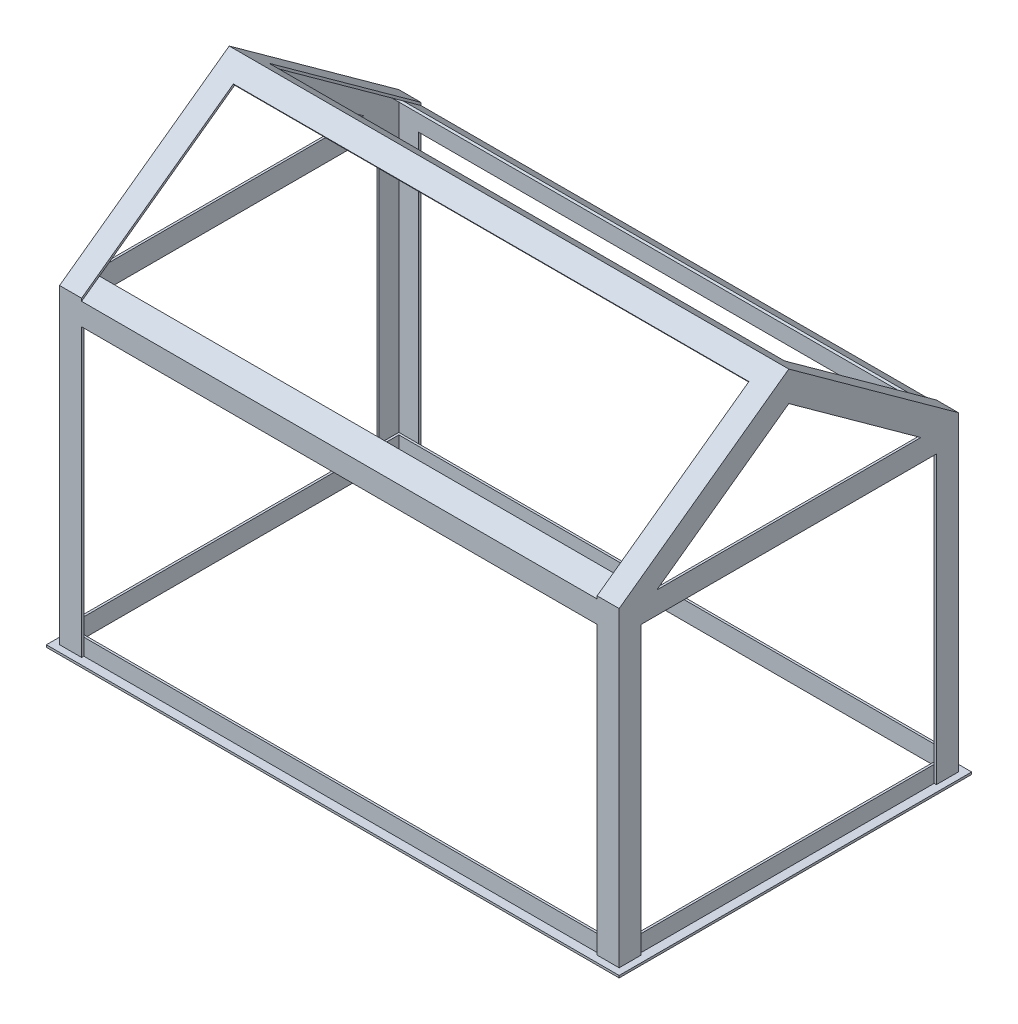
SolidWorks part; units mm, degrees
material "1350 Legierung"
ref_plane "Ebene vorne" through (0, 0, 0) normal (0, 0, 1) x (1, 0, 0)
ref_plane "Ebene oben" through (0, 0, 0) normal (0, 1, 0) x (1, 0, 0)
ref_plane "Ebene rechts" through (0, 0, 0) normal (1, 0, 0) x (0, 0, -1)
sketch "Skizze1" plane through (0, 0, 0) normal (0, 1, 0) x (1, 0, 0)
  line L1 (0, 0) -> (520, 0)
  line L2 (0, 0) -> (0, 320)
  line L3 (0, 320) -> (520, 320)
  line L4 (520, 0) -> (520, 320)
  line L5 (10, 310) -> (510, 310)
  line L6 (10, 310) -> (10, 10)
  line L7 (10, 10) -> (510, 10)
  line L8 (510, 310) -> (510, 10)
  dimension "D1" = 10
  dimension "D2" = 10
  dimension "D3" = 520
  dimension "D4" = 320
  dimension "D5" = 10
  dimension "D6" = 10
extrude "Aufsatz-Linear austragen1" add sketch "Skizze1" along normal blind 2
sketch "Skizze2" plane through (0, 2, 0) normal (0, 1, 0) x (1, 0, 0)
  line L1 (10, 310) -> (510, 310)
  line L2 (10, 310) -> (10, 10)
  line L3 (10, 10) -> (510, 10)
  line L4 (510, 310) -> (510, 10)
  line L5 (8, 312) -> (512, 312)
  line L6 (8, 312) -> (8, 8)
  line L7 (8, 8) -> (512, 8)
  line L8 (512, 312) -> (512, 8)
  dimension "D1" = 2
  dimension "D2" = 2
  dimension "D3" = 2
  dimension "D4" = 2
extrude "Aufsatz-Linear austragen2" add sketch "Skizze2" along normal blind 15
sketch "Skizze3" plane through (0, 2, 0) normal (0, 1, 0) x (1, 0, 0)
  line L0 (8, 294) -> (6, 294)
  line L1 (8, 312) -> (8, 8) construction
  line L2 (6, 294) -> (6, 314)
  line L3 (6, 314) -> (26, 314)
  line L4 (26, 314) -> (26, 312)
  line L5 (512, 312) -> (8, 312) construction
  line L6 (26, 312) -> (8, 312)
  line L7 (8, 312) -> (8, 294)
  line L8 (260, 341.2659) -> (260, -42.352) construction
  line L9 (-21.5346, 160) -> (593.4367, 160) construction
  line L10 (512, 312) -> (512, 294)
  line L11 (494, 312) -> (512, 312)
  line L12 (494, 314) -> (494, 312)
  line L13 (514, 314) -> (494, 314)
  line L14 (514, 294) -> (514, 314)
  line L15 (512, 294) -> (514, 294)
  line L16 (512, 26) -> (514, 26)
  line L17 (514, 26) -> (514, 6)
  line L18 (514, 6) -> (494, 6)
  line L19 (494, 6) -> (494, 8)
  line L20 (494, 8) -> (512, 8)
  line L21 (512, 8) -> (512, 26)
  line L22 (8, 8) -> (8, 26)
  line L23 (26, 8) -> (8, 8)
  line L24 (26, 6) -> (26, 8)
  line L25 (6, 6) -> (26, 6)
  line L26 (6, 26) -> (6, 6)
  line L27 (8, 26) -> (6, 26)
  line L28 (8, 8) -> (512, 8) construction
  line L29 (512, 8) -> (512, 312) construction
  line L30 (512, 8) -> (512, 312) construction
  dimension "D1" = 2
  dimension "D2" = 20
extrude "Aufsatz-Linear austragen3" add sketch "Skizze3" along normal blind 280
sketch "Skizze4" plane through (26, 0, 0) normal (1, 0, 0) x (0, 0, -1)
  line L0 (8, 282) -> (8, 17) construction
  line L1 (6, 282) -> (8, 282)
  line L2 (6, 282) -> (6, 262)
  line L3 (6, 262) -> (8, 262)
  line L4 (8, 282) -> (8, 262)
  dimension "D1" = 20
extrude "Aufsatz-Linear austragen4" add sketch "Skizze4" along normal up to next
ref_plane "Ebene1" through (0, 0, -160) normal (0, 0, 1) x (1, 0, 0)
mirror "Spiegeln1" about plane through (0, 0, -160) normal (0, 0, 1) of "Aufsatz-Linear austragen4"
sketch "Skizze5" plane through (0, 0, -294) normal (0, 0, 1) x (1, 0, 0)
  line L0 (514, 282) -> (514, 2) construction
  line L1 (512, 282) -> (514, 282)
  line L2 (512, 282) -> (512, 262)
  line L3 (512, 262) -> (514, 262)
  line L4 (514, 282) -> (514, 262)
  dimension "D1" = 20
extrude "Aufsatz-Linear austragen5" add sketch "Skizze5" along normal up to next
ref_plane "Ebene2" through (260, 0, 0) normal (1, 0, 0) x (0, 0, -1)
mirror "Spiegeln2" about plane through (260, 0, 0) normal (1, 0, 0) of "Aufsatz-Linear austragen5"
sketch "Skizze7" plane through (6, 0, 0) normal (-1, 0, 0) x (0, 0, 1)
  line L0 (-314, 282) -> (-160, 393.2834)
  line L1 (-160, 393.2834) -> (-6, 282)
  line L2 (-6, 282) -> (-40.147, 282)
  line L3 (-314, 282) -> (-6, 282) construction
  line L4 (-40.147, 282) -> (-160, 368.6081)
  line L5 (-160, 368.6081) -> (-279.853, 282)
  line L6 (-279.853, 282) -> (-314, 282)
  line L7 (-160, -155.1) -> (-160, 155.1) construction
  dimension "D1" = 190
  dimension "D2" = 20
extrude "Aufsatz-Linear austragen7" add sketch "Skizze7" against normal blind 2
mirror "Spiegeln5" about plane through (260, 0, 0) normal (1, 0, 0) of "Aufsatz-Linear austragen7"
ref_axis "Achse1" through (-26, 0, 0) along (1, 0, 0)
sketch "Skizze8" plane through (260, 0, 0) normal (1, 0, 0) x (0, 0, -1)
  line L0 (175.0391, 382.4159) -> (160, 393.2834)
  line L1 (160, 393.2834) -> (314, 282) construction
  line L2 (160, 393.2834) -> (144.9609, 382.4159)
  line L3 (6, 282) -> (160, 393.2834) construction
  line L4 (144.9609, 382.4159) -> (143.7895, 384.0369)
  line L5 (143.7895, 384.0369) -> (160, 395.751)
  line L6 (160, 216.3059) -> (160, -216.3059) construction
  line L7 (160, 395.751) -> (176.2105, 384.0369)
  line L8 (176.2105, 384.0369) -> (175.0391, 382.4159)
  point P5 (0, 0)
  point P14 (0, 0)
  point P15 (0, 0)
  dimension "D1" = 2
  dimension "D2" = 20
extrude "Aufsatz-Linear austragen12" add sketch "Skizze8" along normal up to surface (254 mm away) up to face at (514, 310.8694, -160)
ref_plane "Ebene3" through (260, 395.751, -160) normal (0, -0.5857, 0.8105) x (1, 0, 0)
extrude "Aufsatz-Linear austragen13" add sketch "Skizze8<2>" against normal up to surface (254 mm away) up to face at (6, 310.8694, -160)
sketch "Skizze8<2>" plane through (260, 0, 0) normal (1, 0, 0) x (0, 0, -1) same geometry as "Skizze8"
sketch "Skizze11" plane through (512, 0, 0) normal (-1, 0, 0) x (0, 0, 1)
  line L0 (-314, 282) -> (-312, 282)
  line L1 (-312, 282) -> (-312, 280)
  line L2 (-312, 280) -> (-310.5853, 280)
  line L3 (-310.5853, 280) -> (-310.5853, 282)
  line L4 (-310.5853, 282) -> (-296.6181, 292.093)
  line L5 (-296.6181, 292.093) -> (-297.7895, 293.714)
  line L6 (-175.0391, 382.4159) -> (-314, 282) construction
  line L7 (-297.7895, 293.714) -> (-314, 282)
  point P4 (0, 0)
  dimension "D1" = 2
  dimension "D2" = 20
  dimension "D3" = 2
extrude "Aufsatz-Linear austragen16" add sketch "Skizze11" along normal up to surface (504 mm away) up to face at (8, 221.3935, -160)
mirror "Spiegeln6" about plane through (0, 0, -160) normal (0, 0, 1) of "Aufsatz-Linear austragen16"
sketch "Skizze12" plane through (0, 48.0908, 66.5507) normal (0, -0.5857, -0.8105) x (-1, 0, 0)
  line L0 (-6, 414.4789) -> (-6, 412.4789)
  line L1 (-6, 414.4789) -> (-26, 414.4789)
  line L2 (-6, 412.4789) -> (-26, 412.4789)
  line L3 (-26, 414.4789) -> (-26, 412.4789)
  dimension "D1" = 20
extrude "Aufsatz-Linear austragen17" add sketch "Skizze12" along normal up to surface (171.4452 mm away) up to face at (260, 137, -314)
mirror "Spiegeln10" about plane through (260, 0, 0) normal (1, 0, 0) of "Aufsatz-Linear austragen17"
sketch "Skizze13" plane through (0, 200.0035, -276.7756) normal (0, -0.5857, 0.8105) x (1, 0, 0)
  line L0 (6, 225.0542) -> (6, 227.0542)
  line L1 (6, 225.0542) -> (26, 225.0542)
  line L2 (6, 227.0542) -> (26, 227.0542)
  line L3 (26, 225.0542) -> (26, 227.0542)
  dimension "D1" = 20
extrude "Aufsatz-Linear austragen18" add sketch "Skizze13" along normal up to surface (170 mm away) up to face at (260, 137, -6)
mirror "Spiegeln12" about plane through (260, 0, 0) normal (1, 0, 0) of "Aufsatz-Linear austragen18"
